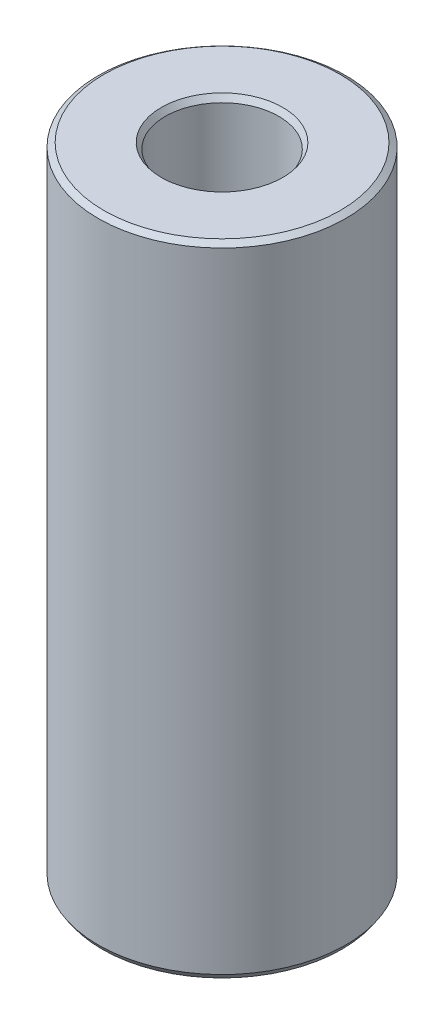
SolidWorks part; units mm, degrees
ref_plane "Front Plane" through (0, 0, 0) normal (0, 0, 1) x (1, 0, 0)
ref_plane "Top Plane" through (0, 0, 0) normal (0, 1, 0) x (1, 0, 0)
ref_plane "Right Plane" through (0, 0, 0) normal (1, 0, 0) x (0, 0, -1)
sketch "Sketch1" plane through (0, 0, 0) normal (0, 1, 0) x (1, 0, 0)
  circle A0 centre (0, 0) radius 50
  dimension "SLEEVE_OD" = 100
extrude "Boss-Extrude1" add sketch "Sketch1" along normal blind 258.0323
sketch "Sketch2" plane through (0, 0, 0) normal (0, 1, 0) x (1, 0, 0)
  circle A0 centre (0, 0) radius 22.9365
  dimension "BORE_D" = 45.8731
extrude "Cut-Extrude1" cut sketch "Sketch2" along normal through all
chamfer "Chamfer1" distance 1.5952 angle 55.515 4 edges at (0, 258.0323, 22.9365) (0, 0, 22.9365) (0, 0, 50) (0, 258.0323, 50) first distance on face at (0, 258.0323, 22.9365) first distance on face at (0, 0, 22.9365) first distance on face at (0, 258.0323, 50)
